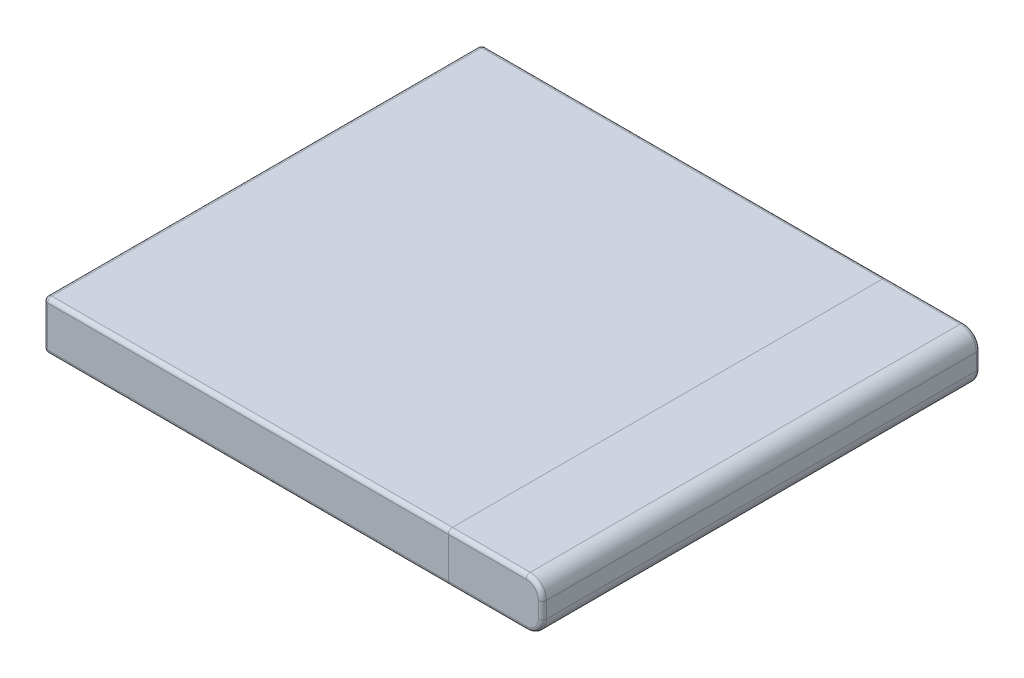
SolidWorks part; units mm, degrees
ref_plane "Front Plane" through (0, 0, 0) normal (0, 0, 1) x (1, 0, 0)
ref_plane "Top Plane" through (0, 0, 0) normal (0, 1, 0) x (1, 0, 0)
ref_plane "Right Plane" through (0, 0, 0) normal (1, 0, 0) x (0, 0, -1)
sketch "Sketch1" plane through (0, 0, 0) normal (0, 1, 0) x (1, 0, 0)
  line L0 (-24.95, -27) -> (24.95, -27)
  line L1 (-24.95, -27) -> (-24.95, 27)
  line L2 (24.95, -27) -> (24.95, 27)
  line L3 (-24.95, 27) -> (24.95, 27)
  line L4 (-24.95, -27) -> (24.95, 27) construction
  line L5 (24.95, -27) -> (-24.95, 27) construction
  point P1 (0, 0)
  dimension "D1" = 49.9
  dimension "D2" = 54
extrude "Boss-Extrude1" add sketch "Sketch1" along normal blind 3 and the other way blind 3
sketch "Sketch4" plane through (24.95, 0, 0) normal (1, 0, 0) x (0, 0, -1)
  line L1 (-27, -3) -> (27, -3)
  line L2 (-27, -3) -> (-27, 3)
  line L3 (-27, 3) -> (27, 3)
  line L4 (27, -3) -> (27, 3)
extrude "Boss-Extrude4" add sketch "Sketch4" along normal blind 11.6 separate body
fillet "Fillet1" radius 2 2 edges at (36.55, -3, 0) (36.55, 3, 0)
fillet "Fillet3" radius 0.5 10 edges at (29.75, -3, 27) (35.9642, -2.4142, 27) (36.55, 0, 27) (35.9642, 2.4142, 27) (29.75, -3, -27) (35.9642, -2.4142, -27) (36.55, 0, -27) (35.9642, 2.4142, -27) (29.75, 3, 27) (29.75, 3, -27)
fillet "Fillet4" radius 0.5 8 edges at (-24.95, 0, 27) (-24.95, 3, 0) (-24.95, 0, -27) (-24.95, -3, 0) (0, -3, -27) (0, 3, -27) (0, -3, 27) (0, 3, 27)
